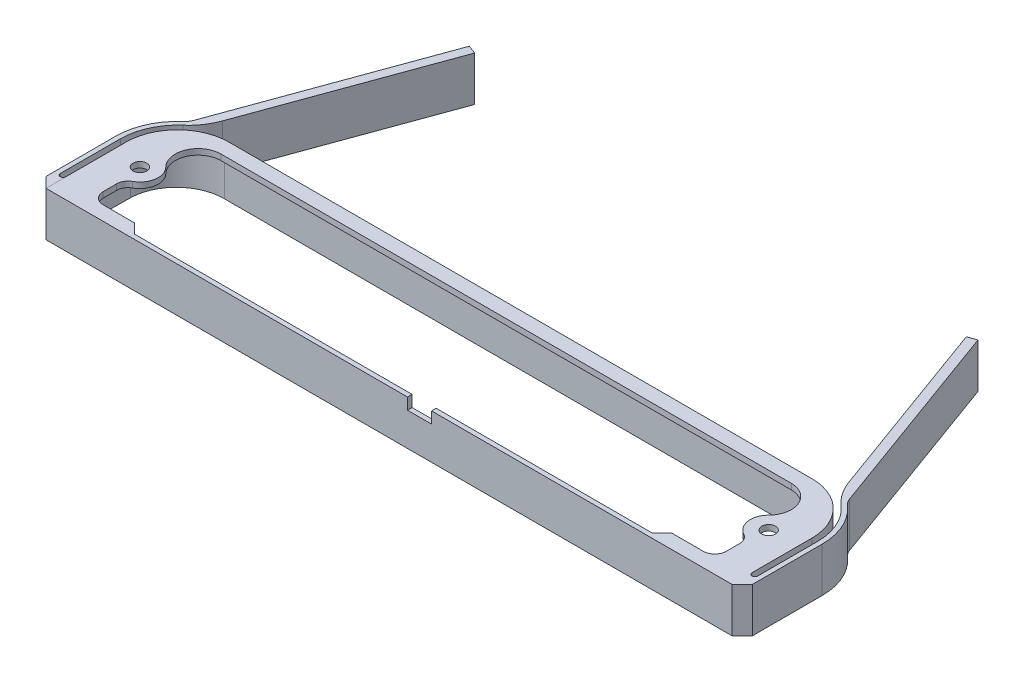
SolidWorks part; units mm, degrees
material "ABS"
ref_plane "Front" through (0, 0, 0) normal (0, 0, 1) x (1, 0, 0)
ref_plane "Top" through (0, 0, 0) normal (0, 1, 0) x (1, 0, 0)
ref_plane "Right" through (0, 0, 0) normal (1, 0, 0) x (0, 0, -1)
ref_axis "X" through (-80.9, 0, 0) along (1, 0, 0)
ref_axis "Y" through (0, -50, 0) along (0, 1, 0)
ref_axis "Z" through (0, 0, -80.9) along (0, 0, 1)
sketch "Sketch1" plane through (0, 0, 0) normal (0, 1, 0) x (1, 0, 0)
  line L0 (-60, 0) -> (-54.5, 0)
  line L2 (-49.8878, 20.5) -> (49.8878, 20.5)
  line L4 (54.5, 0) -> (60, 0)
  line L5 (60, 0) -> (60, 14)
  line L6 (51, 23) -> (-51, 23)
  line L7 (-60, 14) -> (-60, 0)
  line L8 (-54.5, 0) -> (54.5, 0)
  line L9 (-47, 0.8) -> (47, 0.8)
  line L10 (-54.5, 0) -> (-54.5, 0.8) construction
  line L11 (54.5, 0) -> (54.5, 0.8) construction
  line L12 (55, 11.43) -> (-55, 11.43) construction
  line L13 (0, 11.43) -> (0, 0) construction
  line L14 (54.5, 2.5) -> (47, 2.5)
  line L15 (47, 2.5) -> (47, 0.8)
  line L16 (-54.5, 2.5) -> (-47, 2.5)
  line L17 (-47, 2.5) -> (-47, 0.8)
  line L18 (-54.5, 0.8) -> (-54.5, 2.5) construction
  line L19 (-54.5, 0.8) -> (-47, 0.8) construction
  line L20 (54.5, 2.5) -> (54.5, 0.8) construction
  line L21 (47, 0.8) -> (54.5, 0.8) construction
  line L22 (54.5, 8.2693) -> (54.5, 2.5)
  line L23 (-54.5, 2.5) -> (-54.5, 8.2693)
  arc A0 (-52.7279, 13.6833) -> (-49.8878, 20.5) centre (-49.8878, 16.5) cw
  arc A1 (49.8878, 20.5) -> (52.7279, 13.6833) centre (49.8878, 16.5) cw
  arc A2 (60, 14) -> (51, 23) centre (51, 14) ccw
  arc A3 (-51, 23) -> (-60, 14) centre (-51, 14) ccw
  circle A4 centre (55, 11.43) radius 1.2
  circle A5 centre (-55, 11.43) radius 1.2
  arc A6 (52.7279, 13.6833) -> (54.5, 8.2693) centre (55, 11.43) ccw
  arc A7 (-52.7279, 13.6833) -> (-54.5, 8.2693) centre (-55, 11.43) cw
  dimension "D5" = 9
  dimension "D6" = 4
  dimension "D10" = 2.4
  dimension "D13" = 3.2
  dimension "D1" = 120
  dimension "D2" = 5.5
  dimension "D3" = 2.5
  dimension "D4" = 23
  dimension "D7" = 0.8
  dimension "D8" = 11.43
  dimension "D9" = 110
  dimension "D11" = 13
  dimension "D12" = 2.5
extrude "Boss-Extrude1" add sketch "Sketch1" along normal blind 1
sketch "Sketch8" plane through (0, 0, 0) normal (0, -1, 0) x (-1, 0, 0)
  line L0 (-59.2, 0.8) -> (59.2, 0.8)
  line L1 (59.2, 0.8) -> (59.2, 14)
  line L2 (51, 22.2) -> (-51, 22.2)
  line L3 (-59.2, 14) -> (-59.2, 0.8)
  line L4 (60, 0) -> (60, 14)
  line L5 (51, 23) -> (-51, 23)
  line L6 (-60, 14) -> (-60, 0)
  line L7 (-60, 0) -> (60, 0)
  line L8 (60, 0) -> (60, 14)
  line L9 (51, 23) -> (-51, 23)
  line L10 (-60, 14) -> (-60, 0)
  line L11 (-60, 0) -> (60, 0)
  arc A0 (59.2, 14) -> (51, 22.2) centre (51, 14) ccw
  arc A1 (-51, 22.2) -> (-59.2, 14) centre (-51, 14) ccw
  arc A2 (60, 14) -> (51, 23) centre (51, 14) ccw
  arc A3 (-51, 23) -> (-60, 14) centre (-51, 14) ccw
  arc A4 (60, 14) -> (51, 23) centre (51, 14) ccw
  arc A5 (-51, 23) -> (-60, 14) centre (-51, 14) ccw
  dimension "D1" = 0
  dimension "D2" = 0.8
extrude "Boss-Extrude2" add sketch "Sketch8" along normal blind 8.2 from surface starting at face at (55, 1, -10.23)
chamfer "Chamfer1" distance 1 angle 45 7 edges at (59.2, 0, -7.4) (56.7983, 0, -19.7983) (-59.2, 0, -7.4) (-56.7983, 0, -19.7983) (53.1, 0, -0.8) (-53.1, 0, -0.8) (0, 0, -22.2)
sketch "Sketch9" plane through (0, 0, 0) normal (1, 0, 0) x (0, 0, -1)
  line L0 (-2, -7.2) -> (23, -7.2)
  line L1 (23, -7.2) -> (-2, -6.7636)
  line L3 (-2, -6.7636) -> (-2, -7.2)
  dimension "D1" = 25
  dimension "D2" = 1
extrude "Cut-Extrude1" cut sketch "Sketch9" against normal through all both and the other way through all
sketch "Sketch11" plane through (0, 0, 0) normal (0, 0, 1) x (1, 0, 0)
  line L0 (3.25, 1) -> (3.25, -1)
  line L1 (-60, 1) -> (60, 1) construction
  line L2 (3.25, -1) -> (7.45, -1)
  line L3 (7.45, -1) -> (7.45, 1)
  line L4 (7.45, 1) -> (3.25, 1)
  line L5 (5.35, -1) -> (5.35, 1) construction
  line L7 (60, 1) -> (60, -6.7985) construction
  dimension "D1" = 54.65
  dimension "D2" = 4.2
  dimension "D3" = 2
extrude "Cut-Extrude2" cut sketch "Sketch11" against normal up to next
fillet "Fillet1" radius 2 4 edges at (-54.5, 0.5, -8.2693) (-54.5, 0.5, -2.5) (54.5, 0.5, -2.5) (54.5, 0.5, -8.2693)
chamfer "Chamfer2" distance 1.7 angle 45 2 edges at (-47, 0, -0.8) (47, 0, -0.8)
sketch "Sketch12" plane through (0, 0, 0) normal (0, 1, 0) x (1, 0, 0)
  line L0 (-50.876, 24) -> (-50.876, 24.8) construction
  line L1 (-60, 0) -> (60, 0) construction
  line L3 (-70.0161, 72.0463) -> (123.9526, 72.0463) construction
  line L9 (-60, 0) -> (-61.8, 1.8)
  line L10 (7.45, 0) -> (60, 0) construction
  line L11 (0, 38.0905) -> (0, 0) construction
  line L21 (-46.1776, 27.2899) -> (-35, 58)
  line L22 (-35, 58) -> (-36.5035, 58.5472)
  line L23 (-36.5035, 58.5472) -> (-48.0718, 26.7635)
  line L27 (51, 23) -> (-51, 23) construction
  line L31 (-60, 0) -> (-60, 3.5)
  line L32 (-60, 14) -> (-60, 0) construction
  line L34 (-61.8, 1.8) -> (-61.8, 14)
  line L35 (-51, 24.8) -> (-50.876, 24.8)
  line L36 (-61, 3.5) -> (-61, 14)
  line L37 (-51, 24) -> (-50.876, 24)
  line L39 (-51, 24) -> (-51, 24.8) construction
  line L40 (-61, 14) -> (-61.8, 14) construction
  arc A3 (-61.8, 14) -> (-51, 24.8) centre (-51, 14) cw
  arc A4 (-61, 14) -> (-51, 24) centre (-51, 14) cw
  arc A5 (-61, 3.5) -> (-60, 3.5) centre (-60.5, 3.5) ccw
  arc A7 (-51, 23) -> (-60, 14) centre (-51, 14) ccw construction
  arc A8 (-50.876, 24) -> (-46.1776, 27.2899) centre (-50.876, 29) ccw
  arc A9 (-50.876, 24.8) -> (-48.0718, 26.7635) centre (-50.876, 27.7842) ccw
  dimension "D7" = 5
  dimension "D3" = 72.0463
  dimension "D9" = 20
  dimension "D11" = 35
  dimension "D12" = 1.6
  dimension "D14" = 35
  dimension "D2" = 45
  dimension "D4" = 1
  dimension "D5" = 0.8
  dimension "D6" = 3.5
extrude "Boss-Extrude3" [suppressed] add sketch "Sketch12" against normal blind 7 from surface starting at face at (0.8231, 1, -7.7026)
mirror "Mirror2" [suppressed] about plane through (0, 0, 0) normal (1, 0, 0)
sketch "Sketch14" plane through (0, 0, 0) normal (0, 1, 0) x (1, 0, 0)
  line L0 (-57.591, 21.5206) -> (-58.1182, 22.1222) construction
  line L1 (-60, 14) -> (-60, 0) construction
  line L2 (7.45, 0) -> (60, 0) construction
  line L3 (-70.0161, 72.0463) -> (123.9526, 72.0463) construction
  line L9 (-60, 0) -> (-61.8, 1.8)
  line L10 (51, 23) -> (-51, 23) construction
  line L11 (0, 38.0905) -> (0, 0) construction
  line L21 (-54.785, 25.621) -> (-43, 58)
  line L22 (-43, 58) -> (-44.5035, 58.5472)
  line L23 (-44.5035, 58.5472) -> (-57.3554, 23.237)
  line L31 (-60, 0) -> (-60, 3.5)
  line L34 (-61.8, 1.8) -> (-61.8, 14)
  line L36 (-61, 3.5) -> (-61, 14)
  line L40 (-61, 14) -> (-61.8, 14) construction
  arc A3 (-61.8, 14) -> (-58.1182, 22.1222) centre (-51, 14) cw
  arc A4 (-61, 14) -> (-57.591, 21.5206) centre (-51, 14) cw
  arc A5 (-61, 3.5) -> (-60, 3.5) centre (-60.5, 3.5) ccw
  arc A6 (-51, 23) -> (-60, 14) centre (-51, 14) ccw construction
  arc A8 (-57.591, 21.5206) -> (-54.785, 25.621) centre (-64.1819, 29.0412) ccw
  arc A9 (-58.1182, 22.1222) -> (-57.3554, 23.237) centre (-59.9102, 24.1669) ccw
  dimension "D7" = 10
  dimension "D8" = 35
  dimension "D4" = 1
  dimension "D2" = 45
  dimension "D3" = 72.0463
  dimension "D5" = 0.8
  dimension "D6" = 3.5
  dimension "D9" = 20
  dimension "D12" = 1.6
  dimension "D14" = 43
extrude "Boss-Extrude4" add sketch "Sketch14" against normal blind 7.7985 from surface separate body starting at face at (0.8231, 1, -7.7026)
mirror "Mirror5" about plane through (0, 0, 0) normal (1, 0, 0) of "Boss-Extrude4"
equation "\"D3@Sketch12\"=200-127.95373"
